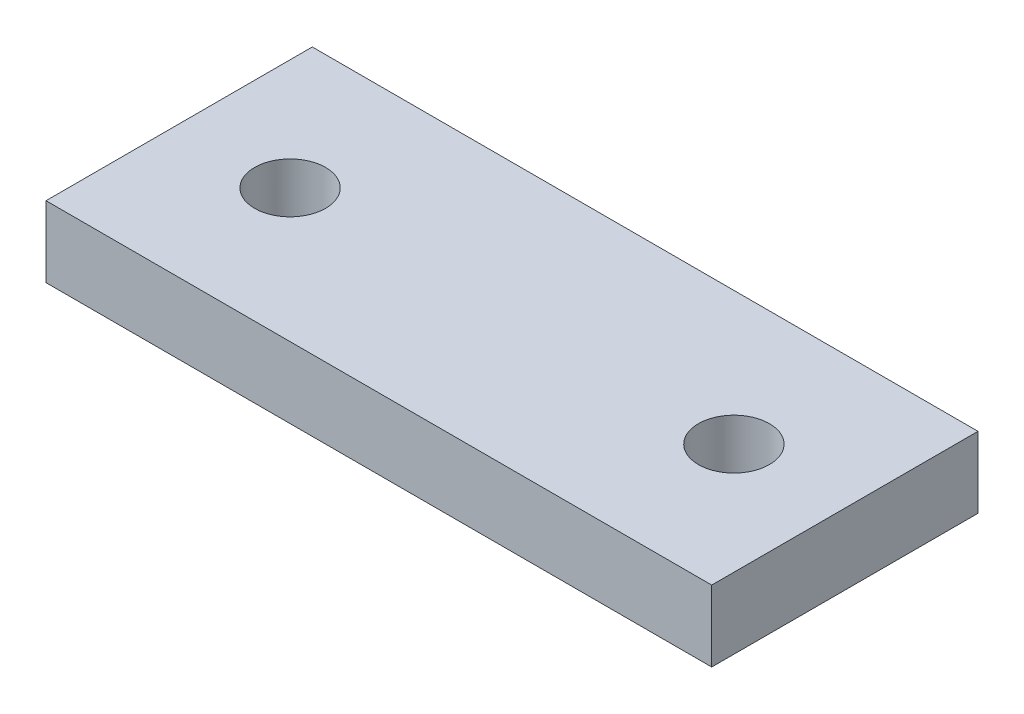
SolidWorks part; units mm, degrees
ref_plane "Front Plane" through (0, 0, 0) normal (0, 0, 1) x (1, 0, 0)
ref_plane "Top Plane" through (0, 0, 0) normal (0, 1, 0) x (1, 0, 0)
ref_plane "Right Plane" through (0, 0, 0) normal (1, 0, 0) x (0, 0, -1)
sketch "Sketch1" plane through (0, 0, 0) normal (0, 0, 1) x (1, 0, 0)
  line L0 (-37.5, 0) -> (37.5, 0)
  line L1 (-37.5, 0) -> (-37.5, -8)
  line L2 (-37.5, -8) -> (37.5, -8)
  line L3 (37.5, -8) -> (37.5, 0)
  line L4 (0, 0) -> (0, -8) construction
  dimension "D1" = 8
  dimension "D2" = 75
extrude "Boss-Extrude1" add sketch "Sketch1" along normal blind 30
sketch "Sketch2" plane through (0, 0, 0) normal (0, 1, 0) x (1, 0, 0)
  line L0 (-37.5, -15) -> (37.5, -15) construction
  line L1 (-37.5, -30) -> (-37.5, 0) construction
  line L2 (37.5, -30) -> (37.5, 0) construction
  line L3 (0, 0) -> (0, -30) construction
  line L4 (37.5, 0) -> (-37.5, 0) construction
  line L5 (37.5, -30) -> (-37.5, -30) construction
  circle A0 centre (-25, -15) radius 4
  circle A1 centre (25, -15) radius 4
  dimension "D1" = 50
  dimension "D2" = 8
extrude "Cut-Extrude1" cut sketch "Sketch2" against normal through all both and the other way through all
